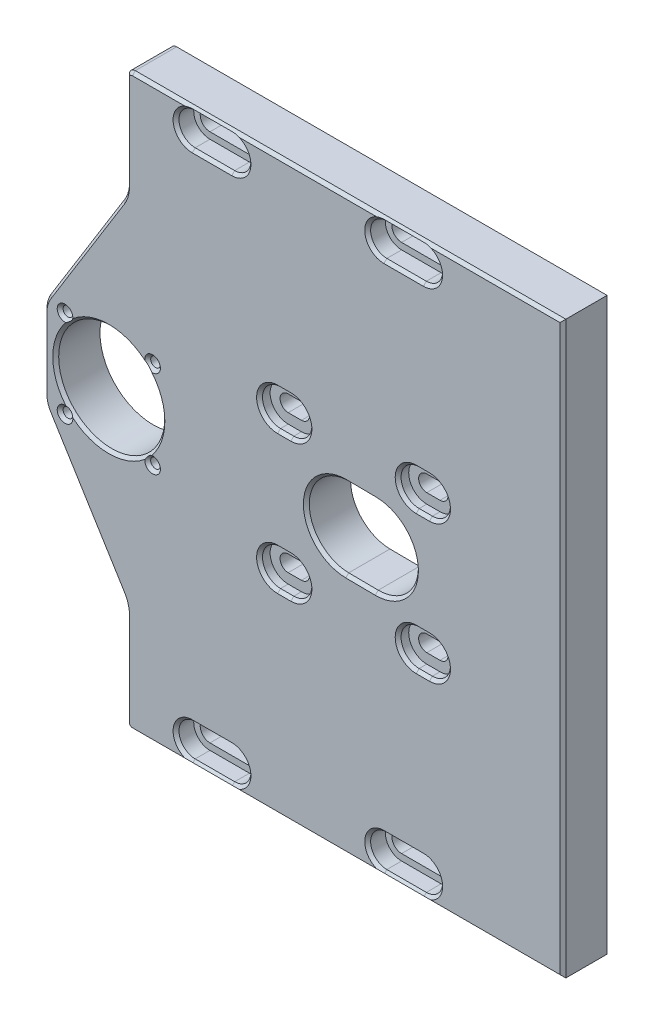
SolidWorks part; units mm, degrees
ref_plane "Front Plane" through (0, 0, 0) normal (0, 0, 1) x (1, 0, 0)
ref_plane "Top Plane" through (0, 0, 0) normal (0, 1, 0) x (1, 0, 0)
ref_plane "Right Plane" through (0, 0, 0) normal (1, 0, 0) x (0, 0, -1)
sketch "Sketch1" plane through (0, 0, 0) normal (0, 0, 1) x (1, 0, 0)
  line L6 (-12, 227) -> (0, 227)
  line L24 (-148, 255) -> (-148, 190) construction
  line L31 (-148, 70) -> (-148, 10) construction
  line L32 (-148, 33.5) -> (-12, 33.5) construction
  line L34 (0, 227) -> (0, 33.5)
  line L36 (-12, 227) -> (-148, 227) construction
  line L37 (-148, 227) -> (-148, 190)
  line L38 (-148, 70) -> (-148, 33.5)
  line L39 (-148, 33.5) -> (-12, 33.5)
  line L43 (-12, 227) -> (-148, 227)
  line L45 (-176, 115.2267) -> (-176, 144.7733)
  line L46 (-176, 144.7733) -> (-148, 190)
  line L47 (-176, 115.2267) -> (-148, 70)
  line L52 (0, 33.5) -> (-12, 33.5)
  circle A8 centre (-154, 130) radius 18
  circle A10 centre (-154, 130) radius 18
  dimension "D1" = 1
extrude "Boss-Extrude1" add sketch "Sketch1" along normal blind 15
sketch "Sketch2" plane through (0, 0, 15) normal (0, 0, 1) x (1, 0, 0)
  circle A1 centre (-139.1508, 115.1508) radius 2.25
  circle A3 centre (-168.8492, 115.1508) radius 2.25
  circle A5 centre (-168.8492, 144.8492) radius 2.25
  circle A7 centre (-139.1508, 144.8492) radius 2.25
hole_wizard "M4x0.7 Tapped Hole1" positions "Sketch3" profile "Sketch4" tap size "M4x0.7" standard "ANSI Metric"
sketch "Sketch3" plane through (0, 0, 15) normal (0, 0, 1) x (1, 0, 0)
  point P0 (-168.8492, 144.8492)
  point P3 (-139.1508, 144.8492)
  point P6 (-139.1508, 115.1508)
  point P9 (-168.8492, 115.1508)
sketch "Sketch4" plane through (-168.8492, 144.8492, 15) normal (1, 0, 0) x (0, -1, 0)
  line L0 (0, 0) -> (0, 20)
  line L1 (0, 20) -> (1.65, 19.0086)
  line L2 (1.65, 19.0086) -> (1.65, 0)
  line L5 (1.65, 0) -> (0, 0)
  line L10 (0, 20) -> (-1.65, 19.0086) construction
  line L11 (0, -6.35) -> (0, 107.95) construction
  dimension "Tap Drill Dia." = 3.3
  dimension "Tap Drill Depth" = 20
  dimension "Drill Angle" = 118
cosmetic thread "Hole Thread1" parameters "D1"=12, "D2"=4
cosmetic thread "Hole Thread2" parameters "D1"=12, "D2"=4
cosmetic thread "Hole Thread7" parameters "D1"=12, "D2"=4
cosmetic thread "Hole Thread8" parameters "D1"=12, "D2"=4
hole_wizard "CBORE SLOT for M6 SHCS1" positions "Sketch5" profile "Sketch6" size "M6" standard "ANSI Metric" slot yes
sketch "Sketch5" plane through (0, 0, 15) normal (0, 0, 1) x (1, 0, 0)
  line L0 (-64, 220) -> (-44, 220) construction
  point P0 (-54, 220)
  point P3 (-119, 220)
  point P6 (-54, 40.5)
  point P9 (-119, 40.5)
  dimension "D1" = 20
sketch "Sketch6" plane through (-54, 220, 15) normal (1, 0, 0) x (0, -1, 0)
  line L0 (0, 0) -> (0, 29.9828)
  line L1 (0, 29.9828) -> (3.3, 28)
  line L2 (3.3, 28) -> (3.3, 6)
  line L3 (3.3, 6) -> (5.5, 6)
  line L4 (5.5, 6) -> (5.5, 0)
  line L5 (5.5, 0) -> (0, 0)
  line L10 (0, 29.9828) -> (-3.3, 28) construction
  line L11 (0, -6.35) -> (0, 107.95) construction
  dimension "Hole Dia." = 6.6
  dimension "Hole Depth" = 28
  dimension "C'Bore Dia." = 11
  dimension "C'Bore Depth" = 6
  dimension "Drill Angle" = 118
sketch "Sketch7" plane through (0, 0, 15) normal (0, 0, 1) x (1, 0, 0)
  line L0 (-73.5, 129.1439) -> (-88.5, 129.1439)
  line L1 (-89.5, 152.6439) -> (-94.5, 152.6439)
  line L2 (-42.5, 152.6439) -> (-47.5, 152.6439)
  line L3 (-42.5, 105.6439) -> (-47.5, 105.6439)
  line L4 (-89.5, 105.6439) -> (-94.5, 105.6439)
  circle A1 centre (-50, 105.6439) radius 2.85 construction
  circle A2 centre (-73.5, 129.1439) radius 13.5
  circle A3 centre (-73.5, 129.1439) radius 13.5
  circle A4 centre (-97, 105.6439) radius 2.85 construction
  circle A5 centre (-97, 152.6439) radius 2.85 construction
  circle A6 centre (-50, 152.6439) radius 2.85 construction
  circle A7 centre (-50, 105.6439) radius 2.85
  circle A8 centre (-97, 105.6439) radius 2.85
  circle A9 centre (-97, 152.6439) radius 2.85
  circle A10 centre (-50, 152.6439) radius 2.85
  dimension "D1" = 1
hole_wizard "Ø1.0mm Dowel Slot1" positions "Sketch8" profile "Sketch9" size "Ø1.0" standard "ANSI Metric" slot yes
sketch "Sketch8" plane through (0, 0, 15) normal (0, 0, 1) x (1, 0, 0)
  line L0 (-86.9991, 129.3233) -> (-50.0009, 128.9645) construction
  point P0 (-68.5, 129.1439)
  dimension "D1" = 37
sketch "Sketch9" plane through (-68.5, 129.1439, 15) normal (1, 0, 0) x (0, -1, 0)
  line L0 (0, 0) -> (0, 36.1116)
  line L1 (0, 36.1116) -> (13.5, 28)
  line L2 (13.5, 28) -> (13.5, 0)
  line L5 (13.5, 0) -> (0, 0)
  line L10 (0, 36.1116) -> (-13.5, 28) construction
  line L11 (0, -6.35) -> (0, 107.95) construction
  dimension "Hole Dia." = 27
  dimension "Hole Depth" = 28
  dimension "Drill Angle" = 118
hole_wizard "CBORE SLOT for M5 Hex Head Bolt1" positions "Sketch10" profile "Sketch11" size "M5" standard "ANSI Metric" slot yes
sketch "Sketch10" plane through (0, 0, 15) normal (0, 0, 1) x (1, 0, 0)
  line L0 (-99.5, 152.6439) -> (-89.5, 152.6439) construction
  point P0 (-94.5, 152.6439)
  point P5 (-94.5, 105.6439)
  point P8 (-47.5, 152.6439)
  point P11 (-47.5, 105.6439)
  dimension "D1" = 10
sketch "Sketch11" plane through (-94.5, 152.6439, 15) normal (1, 0, 0) x (0, -1, 0)
  line L0 (0, 0) -> (0, 29.6524)
  line L1 (0, 29.6524) -> (2.75, 28)
  line L2 (2.75, 28) -> (2.75, 3.58)
  line L3 (2.75, 3.58) -> (6.12, 3.58)
  line L4 (6.12, 3.58) -> (6.12, 0)
  line L5 (6.12, 0) -> (0, 0)
  line L10 (0, 29.6524) -> (-2.75, 28) construction
  line L11 (0, -6.35) -> (0, 107.95) construction
  dimension "Hole Dia." = 5.5
  dimension "Hole Depth" = 28
  dimension "C'Bore Dia." = 12.24
  dimension "C'Bore Depth" = 3.58
  dimension "Drill Angle" = 118
fillet "Fillet1" radius 10 4 edges at (-148, 70, 7.5) (-176, 115.2267, 7.5) (-176, 144.7733, 7.5) (-148, 190, 7.5)
fillet "Fillet2" radius 2 2 edges at (-148, 33.5, 7.5) (-148, 227, 7.5)
chamfer "Chamfer1" distance 1 angle 45 55 edges at (-148.3817, 69.8914, 15) (-162, 92.6134, 15) (-175.6183, 115.3353, 15) (-176, 130, 15) (-175.6183, 144.6647, 15) (-162, 167.3866, 15) (-148.3817, 190.1086, 15) (-148, 208.9225, 15) (-147.4142, 226.4142, 15) (-73, 227, 15) (-73, 33.5, 15) (-147.4142, 34.0858, 15) (-148, 51.3275, 15) (-167.1992, 115.1508, 15) (-137.5008, 115.1508, 15) (-137.5008, 144.8492, 15) (-167.1992, 144.8492, 15) (-86.9991, 129.3233, 15) (-68.6309, 115.6445, 15) (-50.0009, 128.9645, 15) (-68.3691, 142.6433, 15) (-55.87, 105.6439, 15) (-47.5, 99.5239, 15) (-39.13, 105.6439, 15) (-47.5, 111.7639, 15) (-47.5, 146.5239, 15) (-39.13, 152.6439, 15) (-47.5, 158.7639, 15) (-55.87, 152.6439, 15) (-94.5, 99.5239, 15) (-86.13, 105.6439, 15) (-94.5, 111.7639, 15) (-102.87, 105.6439, 15) (-102.87, 152.6439, 15) (-94.5, 146.5239, 15) (-86.13, 152.6439, 15) (-94.5, 158.7639, 15) (0, 130.25, 15) (-119, 35, 15) (-106.8, 40.5, 15) (-119, 46, 15) (-131.2, 40.5, 15) (-41.8, 40.5, 15) (-54, 46, 15) (-66.2, 40.5, 15) (-54, 35, 15) (-119, 225.5, 15) (-131.2, 220, 15) (-119, 214.5, 15) (-106.8, 220, 15) (-54, 225.5, 15) (-66.2, 220, 15) (-54, 214.5, 15) (-41.8, 220, 15) (-136, 130, 15)
